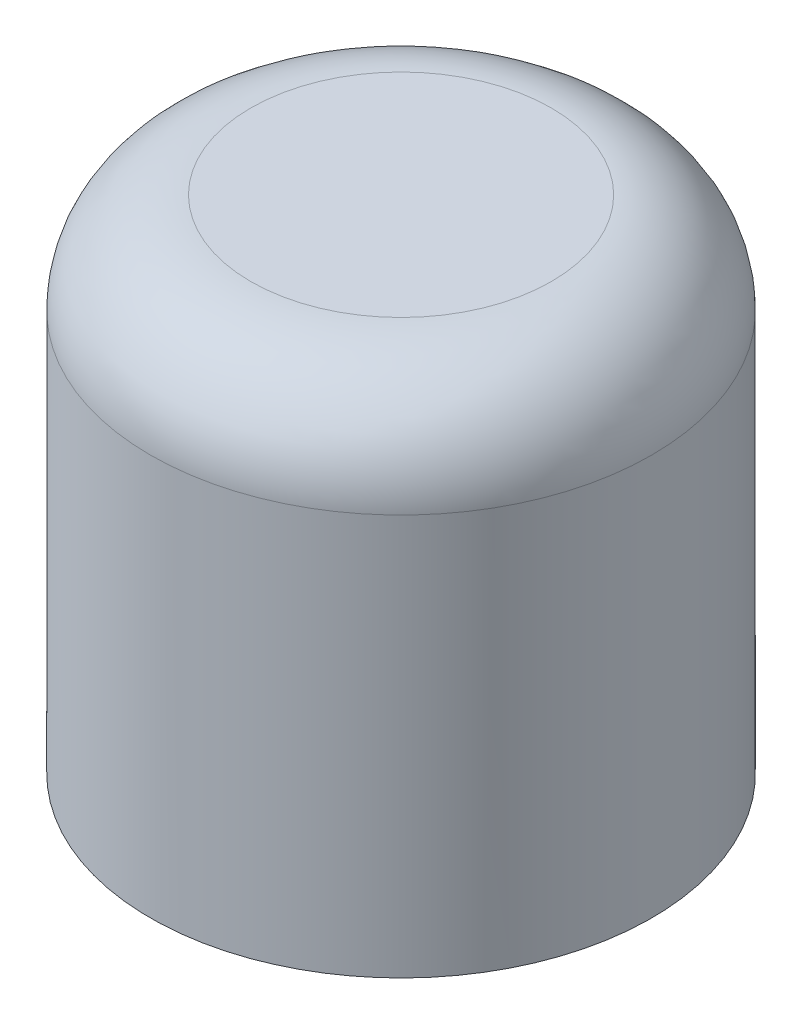
SolidWorks part; units mm, degrees
ref_plane "Front Plane" through (0, 0, 0) normal (0, 0, 1) x (1, 0, 0)
ref_plane "Top Plane" through (0, 0, 0) normal (0, 1, 0) x (1, 0, 0)
ref_plane "Right Plane" through (0, 0, 0) normal (1, 0, 0) x (0, 0, -1)
sketch "Sketch1" plane through (0, 0, 0) normal (0, 1, 0) x (1, 0, 0)
  circle A0 centre (0, 0) radius 17.5
  dimension "D1" = 35
extrude "Boss-Extrude1" add sketch "Sketch1" along normal blind 45
sketch "Sketch2" plane through (0, 0, 0) normal (0, -1, 0) x (1, 0, 0)
  circle A0 centre (0, 0) radius 12
  dimension "D1" = 24
extrude "Cut-Extrude1" cut sketch "Sketch2" against normal blind 20
thread "Thread1" pitch 2 method extrude profile "Thread Profile1" start angle 0, offset 0, length 15, pitch 2, diameter 24
ref_plane "Plane1" through (12, 0, 0) normal (0, 0, 1) x (1, 0, 0)
sketch "Thread Profile1" plane through (12, 0, 0) normal (0, 0, 1) x (1, 0, 0)
  line L0 (0, 0) -> (0, 2) construction
  line L11 (0, 0) -> (0, 1.75)
  line L12 (0, 1.75) -> (-1.0825, 1.125)
  line L13 (-1.0825, 1.125) -> (-1.0825, 0.625)
  line L15 (-1.0825, 0.625) -> (0, 0)
  line L17 (-1.0825, 0.875) -> (0, 0.875) construction
  point P2 (0, 0)
  dimension "Pitch" = 2
  dimension "Profile_Angle" = 60
  dimension "Profile_Land" = 0.5
  dimension "Profile_Height" = 1.0825
sketch "Sketch6" plane through (0, 45, 0) normal (0, 1, 0) x (1, 0, 0)
  circle A0 centre (0, 0) radius 17.5
extrude "Cut-Extrude2" cut sketch "Sketch6" against normal blind 10
fillet "Fillet1" radius 7 1 edges at (0, 35, 17.5)
